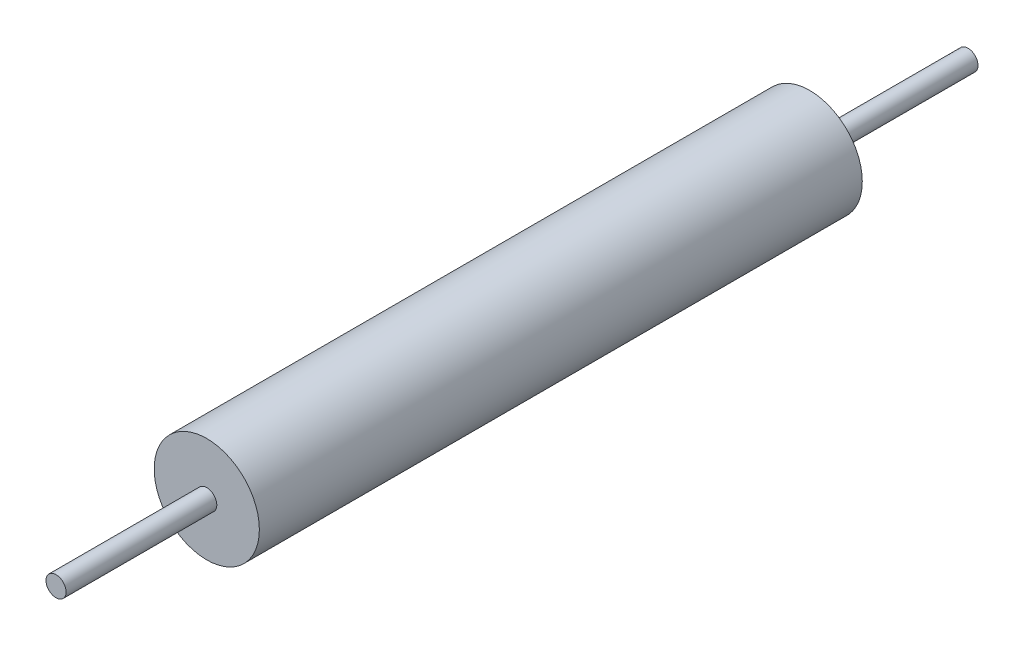
SolidWorks part; units mm, degrees
material "1060 Alloy"
ref_plane "Front Plane" through (0, 0, 0) normal (0, 0, 1) x (1, 0, 0)
ref_plane "Top Plane" through (0, 0, 0) normal (0, 1, 0) x (1, 0, 0)
ref_plane "Right Plane" through (0, 0, 0) normal (1, 0, 0) x (0, 0, -1)
sketch "Sketch1" plane through (0, 0, 0) normal (0, 0, 1) x (1, 0, 0)
  circle A0 centre (0, 0) radius 4
  circle A1 centre (0, 0) radius 3.95
  circle A2 centre (0, 0) radius 20.94
  dimension "D1" = 8
  dimension "D2" = 7.9
  dimension "D3" = 41.88
extrude "Boss-Extrude1" add sketch "Sketch1" along normal blind 240 contours A2 A0 | A0 A1 | A1 region at (-3.9887, 0, 0) region at (0, 0, 0) region at (-20.3477, 0, 0)
extrude "Boss-Extrude2" add sketch "Sketch1<3>" against normal blind 63 contours A0
sketch "Sketch1<3>" plane through (0, 0, 0) normal (0, 0, 1) x (1, 0, 0) same geometry as "Sketch1"
extrude "Boss-Extrude4" add sketch "Sketch1<5>" along normal blind 60 from surface contours A1 | A0 A1 region at (-3.9887, 0, 0) region at (0, 0, 0) starting at face at (20.94, 0, 240)
sketch "Sketch1<5>" plane through (0, 0, 0) normal (0, 0, 1) x (1, 0, 0) same geometry as "Sketch1"
